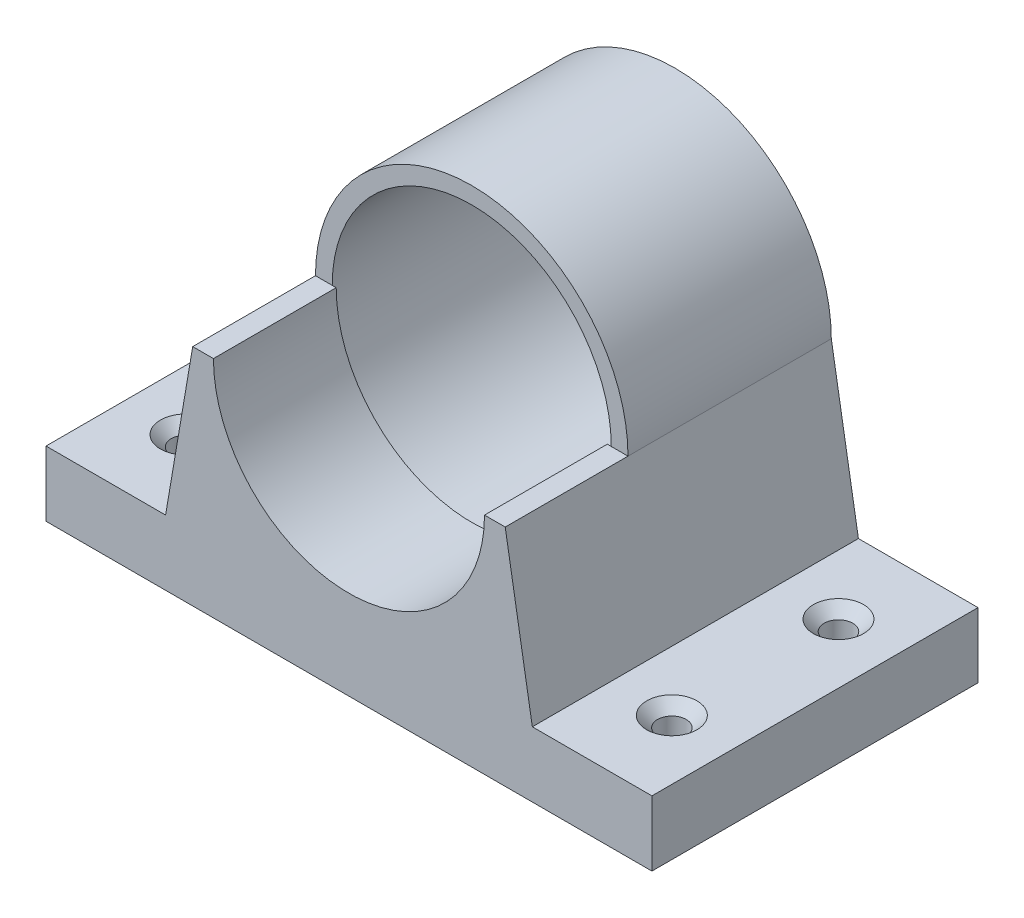
SolidWorks part; units mm, degrees
ref_plane "Front Plane" through (0, 0, 0) normal (0, 0, 1) x (1, 0, 0)
ref_plane "Top Plane" through (0, 0, 0) normal (0, 1, 0) x (1, 0, 0)
ref_plane "Right Plane" through (0, 0, 0) normal (1, 0, 0) x (0, 0, -1)
sketch "Sketch1" plane through (0, 0, 0) normal (0, 0, 1) x (1, 0, 0)
  line L0 (-23, -1.8466) -> (-38, -1.8466)
  line L6 (-38, -1.8466) -> (-38, -6.8466)
  line L7 (23, -1.8466) -> (38, -1.8466)
  line L9 (0, 0) -> (0, 18.1534)
  line L12 (38, -1.8466) -> (38, -6.8466)
  line L13 (-23, -1.8466) -> (-19.6, 18.1534)
  line L14 (19.6, 18.1534) -> (23, -1.8466)
  line L15 (-38, -6.8466) -> (38, -6.8466)
  line L16 (-19.6, 18.1534) -> (-17, 18.1534)
  line L17 (17, 18.1534) -> (19.6, 18.1534)
  circle A2 centre (0, 18.1534) radius 17.5
  arc A3 (-19.6, 18.1534) -> (19.6, 18.1534) centre (0, 18.1534) cw
  arc A4 (-19.6, 18.1534) -> (19.6, 18.1534) centre (0, 18.1534) ccw
  arc A6 (17, 18.1534) -> (-17, 18.1534) centre (0, 18.1534) cw
  dimension "D3" = 35
  dimension "D4" = 17
  dimension "D5" = 19.6
  dimension "D1" = 25
  dimension "D2" = 5
  dimension "D7" = 15
  dimension "D8" = 23
extrude "Boss-Extrude9" add sketch "Sketch1" against normal blind 25.5 contours A3 A4 | A2
extrude "Boss-Extrude10" add sketch "Sketch1<15>" against normal blind 25.5 and the other way blind 15.4 contours L13 L0 L6 L15 L12 L7 L14 A4
sketch "Sketch1<15>" plane through (0, 0, 0) normal (0, 0, 1) x (1, 0, 0) same geometry as "Sketch1"
sketch "Sketch8" plane through (0, -1.8466, 0) normal (0, 1, 0) x (1, 0, 0)
  line L0 (-30.5, -15.4) -> (-30.5, -5.4)
  line L1 (-23, -15.4) -> (-38, -15.4) construction
  line L2 (-23, 25.5) -> (-38, 25.5) construction
  line L3 (-30.5, 25.5) -> (-30.5, 15.5)
  line L4 (0, 0) -> (0, 27.9846) construction
  line L5 (30.5, -15.4) -> (30.5, -5.4)
  line L6 (30.5, 25.5) -> (30.5, 15.5)
  dimension "D1" = 10
hole_wizard "CSK for M3 Flat Head Machine Screw1" positions "Sketch11" profile "Sketch10" countersink size "M3" standard "ANSI Metric" end condition through all
sketch "Sketch11" plane through (0, -1.8466, 0) normal (0, 1, 0) x (1, 0, 0)
  point P0 (-30.5, 15.5)
  point P3 (-30.5, -5.4)
sketch "Sketch10" plane through (-30.5, -1.8466, -15.5) normal (1, 0, 0) x (0, 0, 1)
  line L0 (0, 0) -> (0, 5)
  line L1 (0, 5) -> (1.8, 5)
  line L2 (1.8, 5) -> (1.8, 1.35)
  line L3 (1.8, 1.35) -> (3.15, 0)
  line L5 (3.15, 0) -> (0, 0)
  line L6 (-1.8, 1.35) -> (-3.15, 0) construction
  line L11 (0, -6.35) -> (0, 107.95) construction
  dimension "Thru Hole Dia." = 3.6
  dimension "Thru Hole Depth" = 5
  dimension "Near C'Sink Dia." = 6.3
  dimension "Near C'Sink Angle" = 90
hole_wizard "CSK for M3 Flat Head Machine Screw2" positions "Sketch13" profile "Sketch14" countersink size "M3" standard "ANSI Metric" end condition through all
sketch "Sketch13" plane through (0, -1.8466, 0) normal (0, 1, 0) x (1, 0, 0)
  point P0 (30.5, -5.4)
  point P3 (30.5, 15.5)
sketch "Sketch14" plane through (30.5, -1.8466, 5.4) normal (1, 0, 0) x (0, 0, 1)
  line L0 (0, 0) -> (0, 5)
  line L1 (0, 5) -> (1.8, 5)
  line L2 (1.8, 5) -> (1.8, 1.35)
  line L3 (1.8, 1.35) -> (3.15, 0)
  line L5 (3.15, 0) -> (0, 0)
  line L6 (-1.8, 1.35) -> (-3.15, 0) construction
  line L11 (0, -6.35) -> (0, 107.95) construction
  dimension "Thru Hole Dia." = 3.6
  dimension "Thru Hole Depth" = 5
  dimension "Near C'Sink Dia." = 6.3
  dimension "Near C'Sink Angle" = 90
extrude "Boss-Extrude11" add sketch "Sketch1<19>" along normal blind 15.4 contours L9 A6 L16 A2 | L17 A6 L9 A2 | L16 A4 L17 A2 region at (-18.55, 17.7151, 0) region at (-17.25, 17.9059, 0) region at (12.1994, 5.954, 0)
sketch "Sketch1<19>" plane through (0, 0, 0) normal (0, 0, 1) x (1, 0, 0) same geometry as "Sketch1"
sketch "Sketch15" plane through (0, -6.8466, 0) normal (0, -1, 0) x (-1, 0, 0)
  line L1 (38, -15.4) -> (-38, -15.4)
  line L2 (38, -15.4) -> (38, 25.5)
  line L3 (38, 25.5) -> (-38, 25.5)
  line L4 (-38, -15.4) -> (-38, 25.5)
  circle M5 centre (-30.5, -5.4) radius 1.8
  circle M6 centre (-30.5, 15.5) radius 1.8
  circle M7 centre (30.5, 15.5) radius 1.8
  circle M8 centre (30.5, -5.4) radius 1.8
  line M9 (38, -15.4) -> (38, 25.5)
  line M10 (38, 25.5) -> (-38, 25.5)
  line M11 (-38, 25.5) -> (-38, -15.4)
  line M12 (-38, -15.4) -> (38, -15.4)
extrude "Boss-Extrude12" add sketch "Sketch15" along normal blind 3.175 contours M12 M9 M10 M11 M6 M8 M7 M5 region at (0, -6.8466, -5.05)
